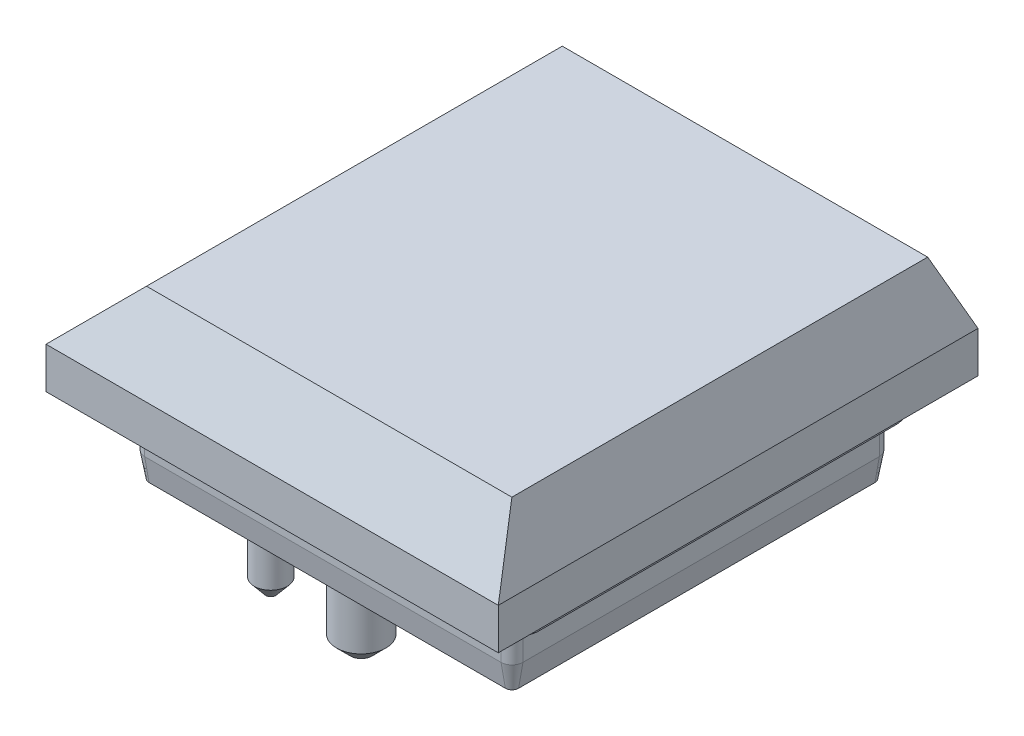
SolidWorks part; units mm, degrees
ref_plane "Front plane" through (0, 0, 0) normal (0, 0, 1) x (1, 0, 0)
ref_plane "Top plane" through (0, 0, 0) normal (0, 1, 0) x (1, 0, 0)
ref_plane "Right plane" through (0, 0, 0) normal (1, 0, 0) x (0, 0, -1)
sketch "Sketch1" plane through (0, 0, 0) normal (0, 1, 0) x (1, 0, 0)
  line L1 (-6.5, -7.5) -> (6.5, -7.5)
  line L2 (-7.5, -6.5) -> (-7.5, 6.5)
  line L3 (-6.5, 7.5) -> (6.5, 7.5)
  line L4 (7.5, -6.5) -> (7.5, 6.5)
  line L5 (-7.5, -7.5) -> (7.5, 7.5) construction
  line L6 (-7.5, 7.5) -> (7.5, -7.5) construction
  arc A0 (-7.5, 6.5) -> (-6.5, 7.5) centre (-6.5, 6.5) cw
  arc A1 (6.5, 7.5) -> (7.5, 6.5) centre (6.5, 6.5) cw
  arc A2 (6.5, -7.5) -> (7.5, -6.5) centre (6.5, -6.5) ccw
  arc A3 (-6.5, -7.5) -> (-7.5, -6.5) centre (-6.5, -6.5) cw
  point P0 (0, 0)
  dimension "D2" = 1
  dimension "D1" = 15
extrude "Boss-Extrude1" add sketch "Sketch1" along normal blind 0.8 contours L1 A2 L4 A1 L3 A0 L2 A3
sketch "Sketch2" plane through (0, 0, 0) normal (0, -1, 0) x (1, 0, 0)
  line L8 (-6.9, 6.5) -> (-6.9, -6.5)
  line L9 (-6.5, -6.9) -> (6.5, -6.9)
  line L10 (6.9, -6.5) -> (6.9, 6.5)
  line L11 (6.5, 6.9) -> (-6.5, 6.9)
  line L12 (-6.9, 6.5) -> (-6.9, -6.5)
  line L13 (-6.5, -6.9) -> (6.5, -6.9)
  line L14 (6.9, -6.5) -> (6.9, 6.5)
  line L15 (6.5, 6.9) -> (-6.5, 6.9)
  arc A8 (-6.5, 6.9) -> (-6.9, 6.5) centre (-6.5, 6.5) ccw
  arc A9 (-6.9, -6.5) -> (-6.5, -6.9) centre (-6.5, -6.5) ccw
  arc A10 (6.5, -6.9) -> (6.9, -6.5) centre (6.5, -6.5) ccw
  arc A11 (6.9, 6.5) -> (6.5, 6.9) centre (6.5, 6.5) ccw
  arc A12 (-6.5, 6.9) -> (-6.9, 6.5) centre (-6.5, 6.5) ccw
  arc A13 (-6.9, -6.5) -> (-6.5, -6.9) centre (-6.5, -6.5) ccw
  arc A14 (6.5, -6.9) -> (6.9, -6.5) centre (6.5, -6.5) ccw
  arc A15 (6.9, 6.5) -> (6.5, 6.9) centre (6.5, 6.5) ccw
  dimension "D1" = 0.6
extrude "Boss-Extrude2" add sketch "Sketch2" along normal blind 1.3
sketch "Sketch3" plane through (0, -1.3, 0) normal (0, -1, 0) x (1, 0, 0)
  line L4 (-6.9, 6.5) -> (-6.9, -6.5)
  line L5 (-6.5, -6.9) -> (6.5, -6.9)
  line L6 (6.9, -6.5) -> (6.9, 6.5)
  line L7 (6.5, 6.9) -> (-6.5, 6.9)
  line L8 (-6.9, 6.5) -> (-6.9, -6.5)
  line L9 (-6.5, -6.9) -> (6.5, -6.9)
  line L10 (6.9, -6.5) -> (6.9, 6.5)
  line L11 (6.5, 6.9) -> (-6.5, 6.9)
  arc A4 (-6.5, 6.9) -> (-6.9, 6.5) centre (-6.5, 6.5) ccw
  arc A5 (-6.9, -6.5) -> (-6.5, -6.9) centre (-6.5, -6.5) ccw
  arc A6 (6.5, -6.9) -> (6.9, -6.5) centre (6.5, -6.5) ccw
  arc A7 (6.9, 6.5) -> (6.5, 6.9) centre (6.5, 6.5) ccw
  arc A8 (-6.5, 6.9) -> (-6.9, 6.5) centre (-6.5, 6.5) ccw
  arc A9 (-6.9, -6.5) -> (-6.5, -6.9) centre (-6.5, -6.5) ccw
  arc A10 (6.5, -6.9) -> (6.9, -6.5) centre (6.5, -6.5) ccw
  arc A11 (6.9, 6.5) -> (6.5, 6.9) centre (6.5, 6.5) ccw
  dimension "D1" = 0
extrude "Boss-Extrude3" add sketch "Sketch3" along normal blind 0.9 draft 10
sketch "Sketch4" plane through (0, -2.2, 0) normal (0, -1, 0) x (1, 0, 0)
  line L0 (-5.9, 0) -> (6.1513, 0) construction
  circle A0 centre (0, 0) radius 1.6
  circle A1 centre (0, -5.5) radius 0.9
  circle A5 centre (0, 5.5) radius 0.9
  dimension "D1" = 3.2
  dimension "D2" = 1.8
  dimension "D3" = 5.5
extrude "Boss-Extrude4" add sketch "Sketch4" along normal blind 2.65
sketch "Sketch5" plane through (0, -2.2, 0) normal (0, -1, 0) x (1, 0, 0)
  line L0 (3.1075, 0) -> (-3.1075, 0) construction
  circle A0 centre (-5.9, 0) radius 0.6
  circle A1 centre (-3.8, -5) radius 0.6
  circle A2 centre (-3.8, 5) radius 0.6
  dimension "D1" = 1.2
  dimension "D2" = 3.8
  dimension "D3" = 5.9
  dimension "D4" = 5
extrude "Boss-Extrude5" add sketch "Sketch5" along normal blind 3
chamfer "Chamfer1" distance 0.5 angle 40 3 edges at (-3.8, -5.2, -5.6) (-5.9, -5.2, -0.6) (-3.8, -5.2, 5.6) first distance on face at (-3.8, -5.2, -5.6) first distance on face at (-5.9, -5.2, -0.6) first distance on face at (-3.8, -5.2, 5.6)
chamfer "Chamfer2" distance 0.5 angle 45 3 edges at (0, -4.85, -6.4) (0, -4.85, -1.6) (0, -4.85, 6.4)
sketch "Sketch6" plane through (0, 0.8, 0) normal (0, 1, 0) x (1, 0, 0)
  line L1 (8.25, 8.75) -> (-8.25, 8.75)
  line L2 (8.25, 8.75) -> (8.25, -8.75)
  line L3 (8.25, -8.75) -> (-8.25, -8.75)
  line L4 (-8.25, 8.75) -> (-8.25, -8.75)
  line L5 (8.25, 8.75) -> (-8.25, -8.75) construction
  line L6 (8.25, -8.75) -> (-8.25, 8.75) construction
  point P0 (0, 0)
  dimension "D1" = 16.5
  dimension "D2" = 17.5
extrude "Boss-Extrude6" add sketch "Sketch6" along normal blind 4
chamfer "Chamfer3" distance 2.5 angle 15 1 edges at (8.25, 4.8, 0) first distance on face at (8.25, 2.8, 0)
chamfer "Chamfer4" distance 2.5 angle 25 2 edges at (-0.3349, 4.8, -8.75) (-0.3349, 4.8, 8.75) first distance on face at (1.516, 2.7, -8.75) first distance on face at (1.516, 2.7, 8.75)
chamfer "Chamfer5" distance 2.5 angle 45 1 edges at (-8.25, 4.8, 0)
ref_plane "Vertical" through (0, 0, 0) normal (0, 0, 1) x (1, 0, 0)
ref_plane "Horisontal" through (0, 0, 0) normal (1, 0, 0) x (0, 0, -1)
